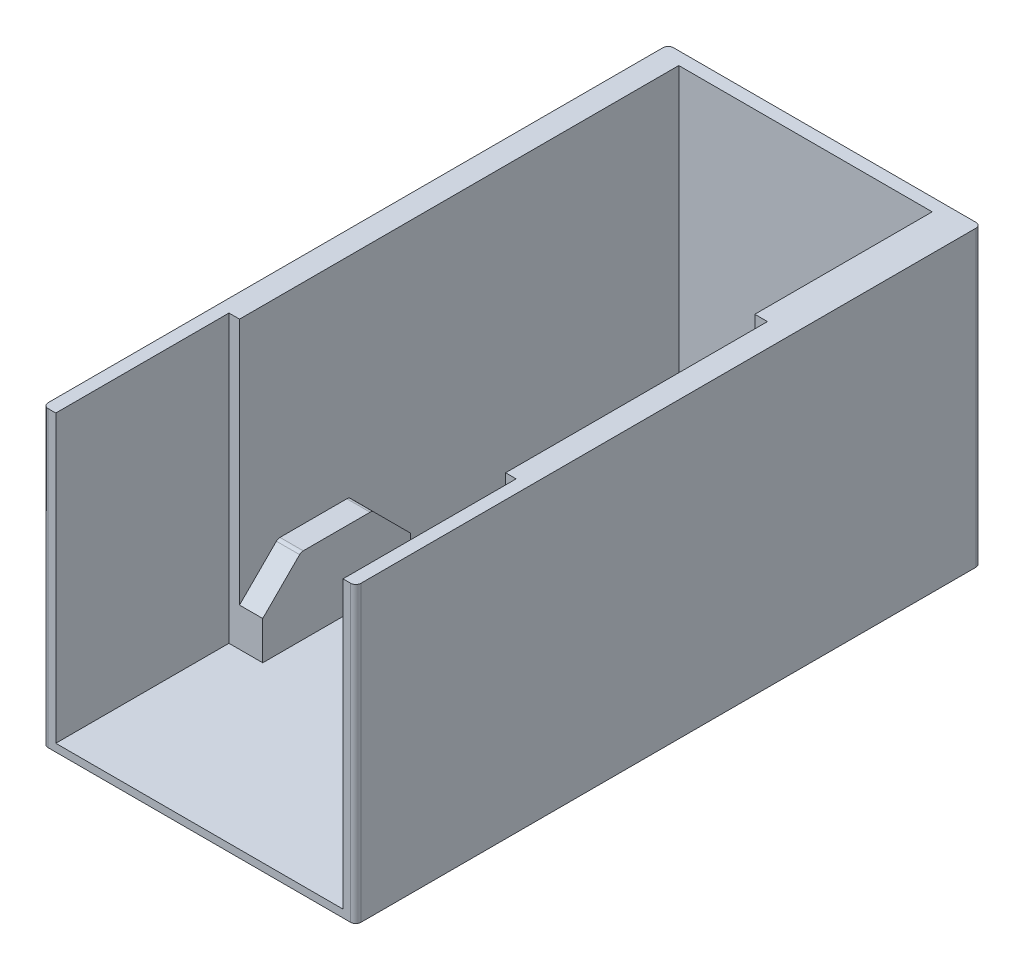
SolidWorks part; units mm, degrees
ref_plane "Front Plane" through (0, 0, 0) normal (0, 0, 1) x (1, 0, 0)
ref_plane "Top Plane" through (0, 0, 0) normal (0, 1, 0) x (1, 0, 0)
ref_plane "Right Plane" through (0, 0, 0) normal (1, 0, 0) x (0, 0, -1)
sketch "Sketch1" plane through (0, 0, 0) normal (0, 1, 0) x (1, 0, 0)
  line L0 (0, 0) -> (0, 2095.5) construction
  line L1 (-863.6, -520.7) -> (863.6, -520.7)
  line L2 (-863.6, -520.7) -> (-863.6, 520.7)
  line L3 (-863.6, 520.7) -> (863.6, 520.7)
  line L4 (863.6, -520.7) -> (863.6, 520.7)
  line L5 (-863.6, -520.7) -> (863.6, 520.7) construction
  line L6 (-863.6, 520.7) -> (863.6, -520.7) construction
  line L7 (-660.4, 520.7) -> (660.4, 520.7)
  line L8 (-660.4, 520.7) -> (-660.4, 1409.7)
  line L9 (-660.4, 1409.7) -> (660.4, 1409.7)
  line L10 (660.4, 520.7) -> (660.4, 1409.7)
  line L12 (-800.1, 1409.7) -> (800.1, 1409.7)
  line L13 (-800.1, 1409.7) -> (-800.1, 2095.5)
  line L14 (-800.1, 2095.5) -> (800.1, 2095.5)
  line L15 (800.1, 1409.7) -> (800.1, 2095.5)
  line L16 (-800.1, 2095.5) -> (723.9, 2095.5)
  line L17 (-800.1, 2095.5) -> (-800.1, 3162.3)
  line L18 (-800.1, 3162.3) -> (723.9, 3162.3)
  line L19 (723.9, 2095.5) -> (723.9, 3162.3)
  point P0 (0, 0)
  point P10 (0, 1409.7)
  point P13 (0, 2095.5)
  dimension "D1" = 1727.2
  dimension "D2" = 1041.4
  dimension "D3" = 1320.8
  dimension "D4" = 889
  dimension "D5" = 1600.2
  dimension "D6" = 685.8
  dimension "D7" = 1524
  dimension "D8" = 1066.8
sketch "Sketch2" plane through (0, 0, 0) normal (0, 1, 0) x (1, 0, 0)
  line L0 (-275, 3062.3) -> (-275, 3012.3) construction
  line L1 (-450, 3012.3) -> (-100, 3012.3)
  line L2 (-450, 3012.3) -> (-450, 2512.3)
  line L3 (-450, 2512.3) -> (-100, 2512.3)
  line L4 (-100, 3012.3) -> (-100, 2512.3)
  line L5 (-500, 3062.3) -> (-50, 3062.3)
  line L6 (-500, 3062.3) -> (-500, 2462.3)
  line L7 (-500, 2462.3) -> (-50, 2462.3)
  line L8 (-50, 3062.3) -> (-50, 2462.3)
  line L9 (-450, 2762.3) -> (-500, 2762.3) construction
  line L10 (100, 3012.3) -> (100, 2512.3)
  line L11 (100, 3012.3) -> (450, 3012.3)
  line L12 (450, 3012.3) -> (450, 2512.3)
  line L13 (100, 2512.3) -> (450, 2512.3)
  line L14 (50, 3062.3) -> (50, 2462.3)
  line L15 (50, 3062.3) -> (500, 3062.3)
  line L16 (500, 3062.3) -> (500, 2462.3)
  line L17 (50, 2462.3) -> (500, 2462.3)
  line L18 (100, 2312.3) -> (100, 1812.3)
  line L19 (100, 2312.3) -> (450, 2312.3)
  line L20 (450, 2312.3) -> (450, 1812.3)
  line L21 (100, 1812.3) -> (450, 1812.3)
  line L22 (50, 2362.3) -> (50, 1762.3)
  line L23 (50, 2362.3) -> (500, 2362.3)
  line L24 (500, 2362.3) -> (500, 1762.3)
  line L25 (50, 1762.3) -> (500, 1762.3)
  line L26 (100, 1612.3) -> (100, 1112.3)
  line L27 (100, 1612.3) -> (450, 1612.3)
  line L28 (450, 1612.3) -> (450, 1112.3)
  line L29 (100, 1112.3) -> (450, 1112.3)
  line L30 (50, 1662.3) -> (50, 1062.3)
  line L31 (50, 1662.3) -> (500, 1662.3)
  line L32 (500, 1662.3) -> (500, 1062.3)
  line L33 (50, 1062.3) -> (500, 1062.3)
  line L34 (100, 912.3) -> (100, 412.3)
  line L35 (100, 912.3) -> (450, 912.3)
  line L36 (450, 912.3) -> (450, 412.3)
  line L37 (100, 412.3) -> (450, 412.3)
  line L38 (50, 962.3) -> (50, 362.3)
  line L39 (50, 962.3) -> (500, 962.3)
  line L40 (500, 962.3) -> (500, 362.3)
  line L41 (50, 362.3) -> (500, 362.3)
  line L42 (-450, 2312.3) -> (-450, 1812.3)
  line L43 (-450, 2312.3) -> (-100, 2312.3)
  line L44 (-100, 2312.3) -> (-100, 1812.3)
  line L45 (-450, 1812.3) -> (-100, 1812.3)
  line L46 (-500, 2362.3) -> (-500, 1762.3)
  line L47 (-500, 2362.3) -> (-50, 2362.3)
  line L48 (-50, 2362.3) -> (-50, 1762.3)
  line L49 (-500, 1762.3) -> (-50, 1762.3)
  line L50 (-450, 1612.3) -> (-450, 1112.3)
  line L51 (-450, 1612.3) -> (-100, 1612.3)
  line L52 (-100, 1612.3) -> (-100, 1112.3)
  line L53 (-450, 1112.3) -> (-100, 1112.3)
  line L54 (-500, 1662.3) -> (-500, 1062.3)
  line L55 (-500, 1662.3) -> (-50, 1662.3)
  line L56 (-50, 1662.3) -> (-50, 1062.3)
  line L57 (-500, 1062.3) -> (-50, 1062.3)
  line L58 (-450, 912.3) -> (-450, 412.3)
  line L59 (-450, 912.3) -> (-100, 912.3)
  line L60 (-100, 912.3) -> (-100, 412.3)
  line L61 (-450, 412.3) -> (-100, 412.3)
  line L62 (-500, 962.3) -> (-500, 362.3)
  line L63 (-500, 962.3) -> (-50, 962.3)
  line L64 (-50, 962.3) -> (-50, 362.3)
  line L65 (-500, 362.3) -> (-50, 362.3)
  line L66 (-450, 3012.3) -> (100, 3012.3) construction
  line L67 (-450, 3012.3) -> (-450, 2312.3) construction
  line L68 (-50, 3062.3) -> (50, 3062.3) construction
  line L69 (0, 3062.3) -> (0, 2095.5) construction
  line L70 (-500, 2462.3) -> (-500, 2362.3)
  line L71 (-550, 3112.3) -> (550, 3112.3)
  line L72 (-550, 3112.3) -> (-550, 312.3)
  line L73 (-550, 312.3) -> (550, 312.3)
  line L74 (550, 3112.3) -> (550, 312.3)
  line L75 (-800.1, 3162.3) -> (723.9, 3162.3) construction
  dimension "D1" = 350
  dimension "D2" = 500
  dimension "D3" = 450
  dimension "D4" = 600
  dimension "D5" = 2
  dimension "D7" = 90
  dimension "D8" = 550
  dimension "D9" = 50
  dimension "D10" = 50
  dimension "D11" = 50
  dimension "D12" = 50
  dimension "D13" = 100
  dimension "D14" = 50
  dimension "D6" = 4
sketch "Resized Everything" plane through (0, 0, 0) normal (0, 1, 0) x (1, 0, 0)
  line L85 (-790.321, 2977.388) -> (-697.865, 2977.388)
  line L86 (-697.865, 2977.388) -> (-697.865, 3039.618)
  line L87 (-790.321, 3039.618) -> (-697.865, 3039.618)
  line L88 (-790.321, 2977.388) -> (-790.321, 3039.618)
  line L89 (-804.545, 2904.49) -> (-683.641, 2904.49)
  line L90 (-683.641, 2904.49) -> (-683.641, 2977.388)
  line L91 (-804.545, 2977.388) -> (-683.641, 2977.388)
  line L92 (-804.545, 2904.49) -> (-804.545, 2977.388)
  line L93 (-800.1, 3039.618) -> (-800.1, 3087.624)
  line L94 (-800.1, 3039.618) -> (-688.086, 3039.618)
  line L95 (-688.086, 3039.618) -> (-688.086, 3087.624)
  line L96 (-800.1, 3087.624) -> (-688.086, 3087.624)
  line L97 (-800.1, 3087.624) -> (-693.42, 3087.624)
  line L98 (-693.42, 3087.624) -> (-693.42, 3162.3)
  line L99 (-800.1, 3162.3) -> (-693.42, 3162.3)
  line L100 (-800.1, 3087.624) -> (-800.1, 3162.3)
  line L101 (-779.093, 3113.3) -> (-779.093, 3106.3)
  line L102 (-779.093, 3113.3) -> (-747.593, 3113.3)
  line L103 (-747.593, 3155.3) -> (-747.593, 3113.3)
  line L104 (-779.093, 3155.3) -> (-747.593, 3155.3)
  line L105 (-779.093, 3155.3) -> (-779.093, 3113.3)
  line L106 (-775.593, 3151.8) -> (-751.093, 3151.8)
  line L107 (-751.093, 3151.8) -> (-751.093, 3116.8)
  line L108 (-775.593, 3116.8) -> (-751.093, 3116.8)
  line L109 (-775.593, 3151.8) -> (-775.593, 3116.8)
  line L110 (-740.593, 3106.3) -> (-740.593, 3064.3)
  line L111 (-740.593, 3064.3) -> (-709.093, 3064.3)
  line L112 (-709.093, 3106.3) -> (-709.093, 3064.3)
  line L113 (-740.593, 3106.3) -> (-709.093, 3106.3)
  line L114 (-737.093, 3102.8) -> (-737.093, 3067.8)
  line L115 (-737.093, 3067.8) -> (-712.593, 3067.8)
  line L116 (-712.593, 3102.8) -> (-712.593, 3067.8)
  line L117 (-737.093, 3102.8) -> (-712.593, 3102.8)
  line L118 (-740.593, 3155.3) -> (-740.593, 3113.3)
  line L119 (-740.593, 3113.3) -> (-709.093, 3113.3)
  line L120 (-709.093, 3155.3) -> (-709.093, 3113.3)
  line L121 (-740.593, 3155.3) -> (-709.093, 3155.3)
  line L122 (-737.093, 3151.8) -> (-737.093, 3116.8)
  line L123 (-737.093, 3151.8) -> (-712.593, 3151.8)
  line L124 (-712.593, 3151.8) -> (-712.593, 3116.8)
  line L125 (-737.093, 3116.8) -> (-712.593, 3116.8)
  line L126 (-740.593, 3008.3) -> (-740.593, 2966.3)
  line L127 (-740.593, 2966.3) -> (-709.093, 2966.3)
  line L128 (-709.093, 3008.3) -> (-709.093, 2966.3)
  line L129 (-740.593, 3008.3) -> (-709.093, 3008.3)
  line L130 (-737.093, 3004.8) -> (-737.093, 2969.8)
  line L131 (-737.093, 2969.8) -> (-712.593, 2969.8)
  line L132 (-712.593, 3004.8) -> (-712.593, 2969.8)
  line L133 (-737.093, 3004.8) -> (-712.593, 3004.8)
  line L134 (-740.593, 3057.3) -> (-740.593, 3015.3)
  line L135 (-740.593, 3015.3) -> (-709.093, 3015.3)
  line L136 (-709.093, 3057.3) -> (-709.093, 3015.3)
  line L137 (-740.593, 3057.3) -> (-709.093, 3057.3)
  line L138 (-737.093, 3053.8) -> (-737.093, 3018.8)
  line L139 (-737.093, 3053.8) -> (-712.593, 3053.8)
  line L140 (-712.593, 3053.8) -> (-712.593, 3018.8)
  line L141 (-737.093, 3018.8) -> (-712.593, 3018.8)
  line L142 (-779.093, 3057.3) -> (-779.093, 3015.3)
  line L143 (-779.093, 3015.3) -> (-747.593, 3015.3)
  line L144 (-747.593, 3057.3) -> (-747.593, 3015.3)
  line L145 (-779.093, 3057.3) -> (-747.593, 3057.3)
  line L146 (-775.593, 3053.8) -> (-775.593, 3018.8)
  line L147 (-775.593, 3018.8) -> (-751.093, 3018.8)
  line L148 (-751.093, 3053.8) -> (-751.093, 3018.8)
  line L149 (-775.593, 3053.8) -> (-751.093, 3053.8)
  line L150 (-779.093, 3106.3) -> (-779.093, 3064.3)
  line L151 (-779.093, 3064.3) -> (-747.593, 3064.3)
  line L152 (-747.593, 3106.3) -> (-747.593, 3064.3)
  line L153 (-779.093, 3106.3) -> (-747.593, 3106.3)
  line L154 (-775.593, 3102.8) -> (-775.593, 3067.8)
  line L155 (-775.593, 3102.8) -> (-751.093, 3102.8)
  line L156 (-751.093, 3102.8) -> (-751.093, 3067.8)
  line L157 (-775.593, 3067.8) -> (-751.093, 3067.8)
  line L158 (-782.593, 3158.8) -> (-705.593, 3158.8)
  line L159 (-705.593, 3158.8) -> (-705.593, 2962.8)
  line L160 (-782.593, 2962.8) -> (-705.593, 2962.8)
  line L161 (-782.593, 3158.8) -> (-782.593, 2962.8)
  line L162 (-779.093, 3008.3) -> (-779.093, 2966.3)
  line L163 (-779.093, 2966.3) -> (-747.593, 2966.3)
  line L164 (-747.593, 3008.3) -> (-747.593, 2966.3)
  line L165 (-779.093, 3008.3) -> (-747.593, 3008.3)
  line L166 (-775.593, 3004.8) -> (-775.593, 2969.8)
  line L167 (-775.593, 3004.8) -> (-751.093, 3004.8)
  line L168 (-751.093, 3004.8) -> (-751.093, 2969.8)
  line L169 (-775.593, 2969.8) -> (-751.093, 2969.8)
sketch "Sketch6" plane through (0, 0, 0) normal (0, 1, 0) x (1, 0, 0)
  line L0 (-800.1, 3162.3) -> (723.9, 3162.3) construction
  line L1 (-748.0935, 2917.905) -> (-748.0935, 3167.3) construction
  line L2 (-809.2275, 2917.905) -> (-686.9595, 2917.905)
  line L3 (-686.9595, 2917.905) -> (-686.9595, 3167.3)
  line L4 (-686.9595, 3167.3) -> (-809.2275, 3167.3)
  line L5 (-696.087, 3048.381) -> (-696.087, 2990.596)
  line L6 (-800.1, 3048.381) -> (-800.1, 2990.596)
  line L7 (-809.2275, 2917.905) -> (-809.2275, 3167.3)
  line L8 (-701.04, 3162.3) -> (-696.087, 3162.3)
  line L9 (-696.087, 3162.3) -> (-696.087, 3092.958)
  line L10 (-804.2275, 2922.905) -> (-809.2275, 2922.905)
  line L11 (-691.9595, 2922.905) -> (-686.9595, 2922.905)
  line L16 (-791.0195, 2990.596) -> (-705.1675, 2990.596)
  line L17 (-705.1675, 2990.596) -> (-705.1675, 3048.381)
  line L18 (-791.0195, 3048.381) -> (-705.1675, 3048.381)
  line L19 (-791.0195, 2990.596) -> (-791.0195, 3048.381)
  line L20 (-804.2275, 2922.905) -> (-691.9595, 2922.905)
  line L21 (-691.9595, 2922.905) -> (-691.9595, 2990.596)
  line L22 (-804.2275, 2990.596) -> (-691.9595, 2990.596)
  line L23 (-804.2275, 2922.905) -> (-804.2275, 2990.596)
  line L24 (-800.1, 3048.381) -> (-800.1, 3092.958)
  line L25 (-800.1, 3048.381) -> (-696.087, 3048.381)
  line L26 (-696.087, 3048.381) -> (-696.087, 3092.958)
  line L27 (-800.1, 3092.958) -> (-696.087, 3092.958)
  line L28 (-800.1, 3092.958) -> (-701.04, 3092.958)
  line L29 (-701.04, 3092.958) -> (-701.04, 3162.3)
  line L30 (-800.1, 3162.3) -> (-701.04, 3162.3)
  line L31 (-800.1, 3092.958) -> (-800.1, 3162.3)
  point P3 (-748.0935, 2922.905)
  dimension "D1" = 239.395
  dimension "D2" = 5
  dimension "D3" = 5
  dimension "D4" = 5
extrude "Boss-Extrude1" add sketch "Sketch6" along normal blind 111.8 contours L2 L1 L20 L23 L22 L6 L24 L31 L30 L4 L7 | L1 L2 L3 L4 L30 L29 L27 L26 L5 L22 L21 L20 | L29 L27 L9 L8 region at (-801.3852, 0, -3070.3406) region at (-694.8018, 0, -3070.3406) region at (-698.5635, 0, -3127.629)
sketch "Sketch7" plane through (0, 0, 0) normal (0, -1, 0) x (1, 0, 0)
  line L0 (-800.1, -3048.381) -> (-800.1, -2990.596) construction
  line L1 (-696.087, -3048.381) -> (-696.087, -2990.596) construction
  line L2 (-800.1, -3048.381) -> (-800.1, -3092.958) construction
  line L3 (-800.1, -3092.958) -> (-696.087, -3092.958) construction
  line L4 (-800.1, -3092.958) -> (-701.04, -3092.958) construction
  line L5 (-701.04, -3092.958) -> (-701.04, -3162.3) construction
  line L6 (-800.1, -3162.3) -> (-701.04, -3162.3) construction
  line L7 (-800.1, -3092.958) -> (-800.1, -3162.3) construction
  line L8 (-701.04, -3162.3) -> (-696.087, -3162.3) construction
  line L9 (-696.087, -3162.3) -> (-696.087, -3092.958) construction
  line L10 (-696.087, -3048.381) -> (-696.087, -3092.958) construction
  line L11 (-800.1, -3048.381) -> (-696.087, -3048.381) construction
  line L12 (-809.2275, -2917.905) -> (-686.9595, -2917.905) construction
  line L13 (-686.9595, -2917.905) -> (-686.9595, -3167.3) construction
  line L14 (-686.9595, -3167.3) -> (-809.2275, -3167.3) construction
  line L15 (-809.2275, -2917.905) -> (-809.2275, -3167.3) construction
  line L16 (-804.2275, -2922.905) -> (-691.9595, -2922.905) construction
  line L17 (-691.9595, -2922.905) -> (-691.9595, -2990.596) construction
  line L18 (-804.2275, -2990.596) -> (-691.9595, -2990.596) construction
  line L19 (-804.2275, -2922.905) -> (-804.2275, -2990.596) construction
  line L20 (-705.1675, -2990.596) -> (-705.1675, -3048.381) construction
  line L21 (-791.0195, -3048.381) -> (-705.1675, -3048.381) construction
  line L22 (-791.0195, -2990.596) -> (-791.0195, -3048.381) construction
  line L23 (-791.0195, -2990.596) -> (-705.1675, -2990.596) construction
  line L24 (-800.1, -3048.381) -> (-800.1, -2990.596)
  line L25 (-696.087, -3048.381) -> (-696.087, -2990.596)
  line L26 (-800.1, -3048.381) -> (-800.1, -3092.958)
  line L27 (-800.1, -3092.958) -> (-696.087, -3092.958)
  line L28 (-800.1, -3092.958) -> (-701.04, -3092.958)
  line L29 (-701.04, -3092.958) -> (-701.04, -3162.3)
  line L30 (-800.1, -3162.3) -> (-701.04, -3162.3)
  line L31 (-800.1, -3092.958) -> (-800.1, -3162.3)
  line L32 (-701.04, -3162.3) -> (-696.087, -3162.3)
  line L33 (-696.087, -3162.3) -> (-696.087, -3092.958)
  line L34 (-696.087, -3048.381) -> (-696.087, -3092.958)
  line L35 (-800.1, -3048.381) -> (-696.087, -3048.381)
  line L36 (-809.2275, -2917.905) -> (-686.9595, -2917.905)
  line L37 (-686.9595, -2917.905) -> (-686.9595, -3167.3)
  line L38 (-686.9595, -3167.3) -> (-809.2275, -3167.3)
  line L39 (-809.2275, -2917.905) -> (-809.2275, -3167.3)
  line L40 (-804.2275, -2922.905) -> (-691.9595, -2922.905)
  line L41 (-691.9595, -2922.905) -> (-691.9595, -2990.596)
  line L42 (-804.2275, -2990.596) -> (-691.9595, -2990.596)
  line L43 (-804.2275, -2922.905) -> (-804.2275, -2990.596)
  line L44 (-705.1675, -2990.596) -> (-705.1675, -3048.381)
  line L45 (-791.0195, -3048.381) -> (-705.1675, -3048.381)
  line L46 (-791.0195, -2990.596) -> (-791.0195, -3048.381)
  line L47 (-791.0195, -2990.596) -> (-705.1675, -2990.596)
extrude "Boss-Extrude2" add sketch "Sketch7" along normal blind 3 contours L39 L38 L37 L36
sketch "Sketch8" plane through (0, 0, 0) normal (0, 1, 0) x (1, 0, 0)
  line L0 (-691.9595, 2922.905) -> (-686.9595, 2922.905) construction
  line L1 (-804.2275, 2922.905) -> (-809.2275, 2922.905) construction
  line L2 (-800.1, 3048.381) -> (-800.1, 2990.596) construction
  line L3 (-696.087, 3048.381) -> (-696.087, 2990.596) construction
  line L4 (-800.1, 3048.381) -> (-800.1, 3092.958) construction
  line L5 (-800.1, 3092.958) -> (-696.087, 3092.958) construction
  line L6 (-800.1, 3092.958) -> (-701.04, 3092.958) construction
  line L7 (-701.04, 3092.958) -> (-701.04, 3162.3) construction
  line L8 (-800.1, 3162.3) -> (-701.04, 3162.3) construction
  line L9 (-800.1, 3092.958) -> (-800.1, 3162.3) construction
  line L10 (-804.2275, 2922.905) -> (-691.9595, 2922.905) construction
  line L11 (-691.9595, 2922.905) -> (-691.9595, 2990.596) construction
  line L12 (-804.2275, 2990.596) -> (-691.9595, 2990.596) construction
  line L13 (-804.2275, 2922.905) -> (-804.2275, 2990.596) construction
  line L14 (-701.04, 3162.3) -> (-696.087, 3162.3) construction
  line L15 (-696.087, 3162.3) -> (-696.087, 3092.958) construction
  line L16 (-696.087, 3048.381) -> (-696.087, 3092.958) construction
  line L17 (-800.1, 3048.381) -> (-696.087, 3048.381) construction
  line L18 (-809.2275, 2917.905) -> (-686.9595, 2917.905) construction
  line L19 (-686.9595, 2917.905) -> (-686.9595, 3167.3) construction
  line L20 (-686.9595, 3167.3) -> (-809.2275, 3167.3) construction
  line L21 (-809.2275, 2917.905) -> (-809.2275, 3167.3) construction
  line L22 (-705.1675, 2990.596) -> (-705.1675, 3048.381) construction
  line L23 (-791.0195, 3048.381) -> (-705.1675, 3048.381) construction
  line L24 (-791.0195, 2990.596) -> (-791.0195, 3048.381) construction
  line L25 (-791.0195, 2990.596) -> (-705.1675, 2990.596) construction
  line L26 (-691.9595, 2922.905) -> (-686.9595, 2922.905)
  line L27 (-804.2275, 2922.905) -> (-809.2275, 2922.905)
  line L28 (-800.1, 3048.381) -> (-800.1, 2990.596)
  line L29 (-696.087, 3048.381) -> (-696.087, 2990.596)
  line L30 (-800.1, 3048.381) -> (-800.1, 3092.958)
  line L31 (-800.1, 3092.958) -> (-696.087, 3092.958)
  line L32 (-800.1, 3092.958) -> (-701.04, 3092.958)
  line L33 (-701.04, 3092.958) -> (-701.04, 3162.3)
  line L34 (-800.1, 3162.3) -> (-701.04, 3162.3)
  line L35 (-800.1, 3092.958) -> (-800.1, 3162.3)
  line L36 (-804.2275, 2922.905) -> (-691.9595, 2922.905)
  line L37 (-691.9595, 2922.905) -> (-691.9595, 2990.596)
  line L38 (-804.2275, 2990.596) -> (-691.9595, 2990.596)
  line L39 (-804.2275, 2922.905) -> (-804.2275, 2990.596)
  line L40 (-701.04, 3162.3) -> (-696.087, 3162.3)
  line L41 (-696.087, 3162.3) -> (-696.087, 3092.958)
  line L42 (-696.087, 3048.381) -> (-696.087, 3092.958)
  line L43 (-800.1, 3048.381) -> (-696.087, 3048.381)
  line L44 (-809.2275, 2917.905) -> (-686.9595, 2917.905)
  line L45 (-686.9595, 2917.905) -> (-686.9595, 3167.3)
  line L46 (-686.9595, 3167.3) -> (-809.2275, 3167.3)
  line L47 (-809.2275, 2917.905) -> (-809.2275, 3167.3)
  line L48 (-705.1675, 2990.596) -> (-705.1675, 3048.381)
  line L49 (-791.0195, 3048.381) -> (-705.1675, 3048.381)
  line L50 (-791.0195, 2990.596) -> (-791.0195, 3048.381)
  line L51 (-791.0195, 2990.596) -> (-705.1675, 2990.596)
  line M17 (-696.087, 2990.596) -> (-696.087, 3092.958)
  line M21 (-800.1, 3162.3) -> (-800.1, 2990.596)
extrude "Boss-Extrude3" add sketch "Sketch8" along normal blind 30 contours L38 L50 L43 M21 | L48 L38 L43 M17 region at (-700.6273, 0, -3019.4885) region at (-795.5597, 0, -3019.4885)
ref_plane "Plane1" through (-748.0935, 0, 0) normal (1, 0, 0) x (0, 0, -1)
sketch "Sketch9" plane through (-791.0195, 0, 0) normal (1, 0, 0) x (0, 0, -1)
  line L0 (2990.596, 15) -> (3005.596, 30)
  line L1 (3019.4885, 30) -> (3019.4885, 0) construction
  line L2 (3048.381, 15) -> (3033.381, 30)
  line L4 (2990.596, 0) -> (3048.381, 0)
  line L5 (3048.381, 0) -> (3048.381, 30)
  line L6 (3048.381, 30) -> (2990.596, 30)
  line L7 (2990.596, 30) -> (2990.596, 0)
  line L8 (2990.596, 0) -> (3048.381, 0)
  line L9 (3048.381, 0) -> (3048.381, 30)
  line L10 (3048.381, 30) -> (2990.596, 30)
  line L11 (2990.596, 30) -> (2990.596, 0)
  line M8 (3048.381, 0) -> (3048.381, 30)
  line M9 (3048.381, 30) -> (2990.596, 30)
  line M10 (2990.596, 30) -> (2990.596, 0)
  dimension "D2" = 45
  dimension "D1" = 0
extrude "Cut-Extrude1" cut sketch "Sketch9" against normal up to surface (9.0805 mm away) contours L0 M10 M9 | L2 M8 M9 region at (-791.0195, 25, -2995.596) region at (-791.0195, 25, -3043.381) up to face at (-800.1, 47.2667, -3067.0923)
sketch "Sketch10" plane through (-705.1675, 0, 0) normal (-1, 0, 0) x (0, 0, 1)
  line L0 (-3048.381, 15) -> (-3033.381, 30) construction
  line L1 (-2990.596, 15) -> (-3005.596, 30) construction
  line L2 (-3048.381, 15) -> (-3033.381, 30)
  line L3 (-2990.596, 15) -> (-3005.596, 30)
  line L4 (-3048.381, 0) -> (-2990.596, 0)
  line L5 (-3048.381, 30) -> (-3048.381, 0)
  line L6 (-2990.596, 30) -> (-3048.381, 30)
  line L7 (-2990.596, 0) -> (-2990.596, 30)
  line L8 (-3048.381, 0) -> (-2990.596, 0)
  line L9 (-3048.381, 30) -> (-3048.381, 0)
  line L10 (-2990.596, 30) -> (-3048.381, 30)
  line L11 (-2990.596, 0) -> (-2990.596, 30)
  line M6 (-2990.596, 0) -> (-2990.596, 30)
  line M7 (-2990.596, 30) -> (-3048.381, 30)
  line M8 (-3048.381, 30) -> (-3048.381, 0)
  dimension "D1" = 0
extrude "Cut-Extrude2" cut sketch "Sketch10" against normal up to surface (9.0805 mm away) contours L2 M8 M7 | L3 M6 M7 region at (-705.1675, 25, -3043.381) region at (-705.1675, 25, -2995.596) up to face at (-696.087, 47.2667, -3043.9783)
fillet "Fillet1" radius 2 8 edges at (-686.9595, 55.9, -2922.905) (-686.9595, 54.4, -3167.3) (-809.2275, 54.4, -3167.3) (-809.2275, 55.9, -2922.905) (-700.6272, 30, -3033.381) (-700.6272, 30, -3005.596) (-795.5598, 30, -3033.381) (-795.5598, 30, -3005.596) tangent propagation no
sketch "Sketch11" plane through (0, 0, 0) normal (0, 1, 0) x (-1, 0, 0)
  line L0 (804.2275, -2922.905) -> (691.9595, -2922.905)
  line L18 (791.0195, -3048.381) -> (791.0195, -2990.596)
  line L19 (791.0195, -2990.596) -> (804.2275, -2990.596)
  line L20 (804.2275, -2990.596) -> (804.2275, -2922.905)
  line L21 (804.2275, -2922.905) -> (807.2275, -2922.905)
  line L22 (809.2275, -2924.905) -> (809.2275, -2917.905)
  line L23 (809.2275, -2917.905) -> (686.9595, -2917.905)
  line L24 (686.9595, -2917.905) -> (686.9595, -2924.905)
  line L25 (688.9595, -2922.905) -> (691.9595, -2922.905)
  line L26 (691.9595, -2922.905) -> (691.9595, -2990.596)
  line L27 (691.9595, -2990.596) -> (705.1675, -2990.596)
  line L28 (705.1675, -2990.596) -> (705.1675, -3048.381)
  line L29 (705.1675, -3048.381) -> (696.087, -3048.381)
  line L30 (696.087, -3048.381) -> (696.087, -3092.958)
  line L31 (696.087, -3092.958) -> (701.04, -3092.958)
  line L32 (701.04, -3092.958) -> (701.04, -3162.3)
  line L33 (701.04, -3162.3) -> (800.1, -3162.3)
  line L34 (800.1, -3162.3) -> (800.1, -3048.381)
  line L35 (800.1, -3048.381) -> (791.0195, -3048.381)
  line L36 (791.0195, -3048.381) -> (791.0195, -2990.596)
  line L37 (791.0195, -2990.596) -> (804.2275, -2990.596)
  line L38 (804.2275, -2990.596) -> (804.2275, -2922.905)
  line L39 (804.2275, -2922.905) -> (807.2275, -2922.905)
  line L40 (809.2275, -2924.905) -> (809.2275, -2917.905)
  line L41 (809.2275, -2917.905) -> (686.9595, -2917.905)
  line L42 (686.9595, -2917.905) -> (686.9595, -2924.905)
  line L43 (688.9595, -2922.905) -> (691.9595, -2922.905)
  line L44 (691.9595, -2922.905) -> (691.9595, -2990.596)
  line L45 (691.9595, -2990.596) -> (705.1675, -2990.596)
  line L46 (705.1675, -2990.596) -> (705.1675, -3048.381)
  line L47 (705.1675, -3048.381) -> (696.087, -3048.381)
  line L48 (696.087, -3048.381) -> (696.087, -3092.958)
  line L49 (696.087, -3092.958) -> (701.04, -3092.958)
  line L50 (701.04, -3092.958) -> (701.04, -3162.3)
  line L51 (701.04, -3162.3) -> (800.1, -3162.3)
  line L52 (800.1, -3162.3) -> (800.1, -3048.381)
  line L53 (800.1, -3048.381) -> (791.0195, -3048.381)
  arc A2 (809.2275, -2924.905) -> (807.2275, -2922.905) centre (807.2275, -2924.905) ccw
  arc A3 (688.9595, -2922.905) -> (686.9595, -2924.905) centre (688.9595, -2924.905) ccw
  arc A4 (809.2275, -2924.905) -> (807.2275, -2922.905) centre (807.2275, -2924.905) ccw
  arc A5 (688.9595, -2922.905) -> (686.9595, -2924.905) centre (688.9595, -2924.905) ccw
  line M24 (804.2275, -2922.905) -> (807.2275, -2922.905)
  arc M25 (807.2275, -2922.905) -> (809.2275, -2924.905) centre (807.2275, -2924.905) cw
  line M26 (809.2275, -2924.905) -> (809.2275, -2917.905)
  line M27 (809.2275, -2917.905) -> (686.9595, -2917.905)
  line M28 (686.9595, -2917.905) -> (686.9595, -2924.905)
  arc M29 (686.9595, -2924.905) -> (688.9595, -2922.905) centre (688.9595, -2924.905) cw
  line M30 (688.9595, -2922.905) -> (691.9595, -2922.905)
  dimension "D1" = 0
extrude "Cut-Extrude3" cut sketch "Sketch11" against normal through all contours L0 M24 M25 M26 M27 M28 M29 M30 region at (-748.0935, 0, -2920.4133)
equation "\"alpha\"= 1"
equation "\"bin_width\"= 0.5"
equation "\"bin_depth\"= 0.35"
equation "\"bin_height\"= 0.35"
